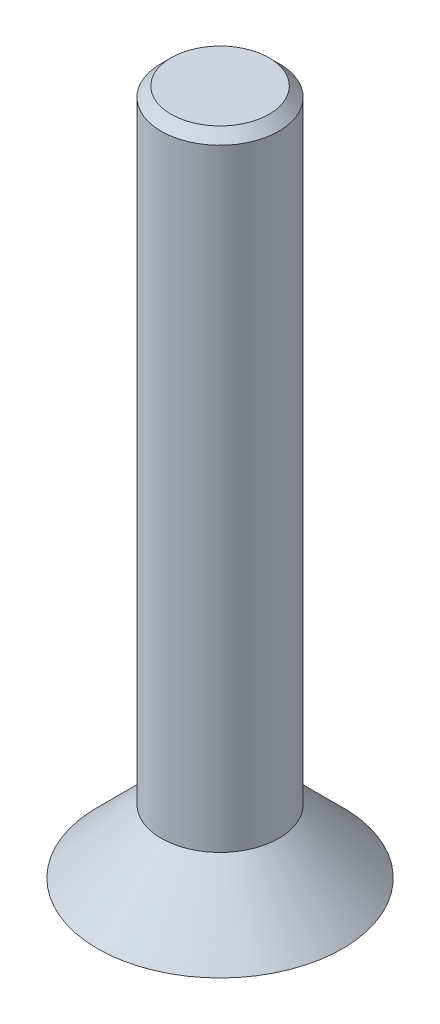
SolidWorks part; units mm, degrees
material "铸造合金钢"
ref_plane "前视基准面" through (0, 0, 0) normal (0, 0, 1) x (1, 0, 0)
ref_plane "上视基准面" through (0, 0, 0) normal (0, 1, 0) x (1, 0, 0)
ref_plane "右视基准面" through (0, 0, 0) normal (1, 0, 0) x (0, 0, -1)
sketch "草图1" plane through (0, 0, 0) normal (0, 1, 0) x (1, 0, 0)
  line L1 (0, -0.866) -> (0.75, -0.433)
  line L2 (0.75, -0.433) -> (0.75, 0.433)
  line L3 (0.75, 0.433) -> (0, 0.866)
  line L4 (0, 0.866) -> (-0.75, 0.433)
  line L5 (-0.75, 0.433) -> (-0.75, -0.433)
  line L6 (-0.75, -0.433) -> (0, -0.866)
  circle A0 centre (0, 0) radius 2.5
  circle A1 centre (0, 0) radius 0.75 construction
  dimension "D1" = 5
  dimension "D2" = 1.5
extrude "凸台-拉伸1" add sketch "草图1" along normal blind 1.3
chamfer "倒角1" distance 1.3 angle 45 1 edges at (0, 1.3, 2.5)
sketch "草图2" plane through (0, 1.3, 0) normal (0, 1, 0) x (1, 0, 0)
  circle A0 centre (0, 0) radius 1.2
  dimension "D1" = 2.4
extrude "凸台-拉伸2" add sketch "草图2" along normal blind 12.7
chamfer "倒角2" distance 0.2 angle 45 1 edges at (0, 14, 1.2)
